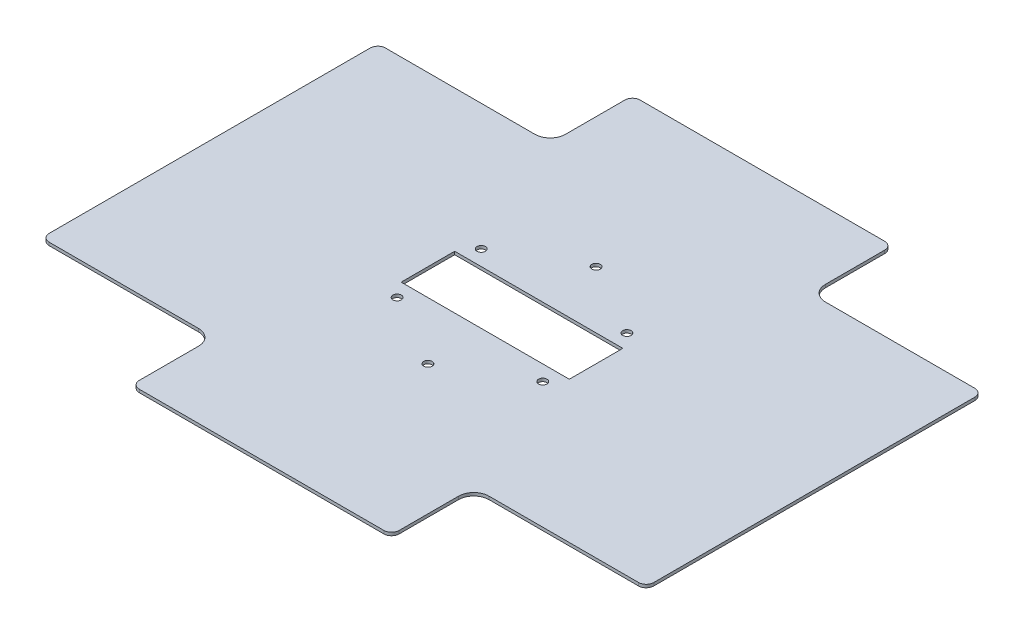
SolidWorks part; units mm, degrees
material "7075-T6, Пластина (SS)"
ref_plane "Спереди" through (0, 0, 0) normal (0, 0, 1) x (1, 0, 0)
ref_plane "Сверху" through (0, 0, 0) normal (0, 1, 0) x (1, 0, 0)
ref_plane "Справа" through (0, 0, 0) normal (1, 0, 0) x (0, 0, -1)
sketch "Эскиз1" plane through (0, 0, 0) normal (0, 1, 0) x (1, 0, 0)
  line L1 (-80, -163.8055) -> (80, -163.8055)
  line L2 (-197.7687, -105) -> (-197.7687, 105)
  line L3 (-80, 163.8055) -> (80, 163.8055)
  line L4 (197.7687, -105) -> (197.7687, 105)
  line L5 (-236.4266, 144.4996) -> (-147.9018, 144.4996) construction
  line L6 (-147.9018, 144.4996) -> (286.4952, 144.4996) construction
  line L18 (-284.5497, 0) -> (284.3305, 0) construction
  line L19 (-160.9018, 110) -> (-134.9018, 110)
  line L20 (-160.9018, 110) -> (-160.9018, 0)
  line L21 (-160.9018, 0) -> (-134.9018, 0)
  line L22 (-134.9018, 110) -> (-134.9018, 0)
  line L23 (-147.9018, -182.6295) -> (-147.9018, 219.9923) construction
  line L24 (-160.9018, 0) -> (-134.9018, 0)
  line L25 (-160.9018, 0) -> (-160.9018, -110)
  line L26 (-160.9018, -110) -> (-134.9018, -110)
  line L27 (-134.9018, 0) -> (-134.9018, -110)
  line L28 (-97.9018, -119.4996) -> (-197.9018, -119.4996)
  line L29 (-97.9018, 169.4996) -> (-197.9018, 169.4996)
  line L30 (-97.9018, 169.4996) -> (-97.9018, 119.4996)
  line L31 (-97.9018, 119.4996) -> (-197.9018, 119.4996)
  line L32 (-197.9018, 169.4996) -> (-197.9018, 119.4996)
  line L33 (-97.9018, 169.4996) -> (-197.9018, 119.4996) construction
  line L34 (-97.9018, 119.4996) -> (-197.9018, 169.4996) construction
  line L35 (-197.9018, -169.4996) -> (-197.9018, -119.4996)
  line L36 (-97.9018, -169.4996) -> (-197.9018, -169.4996)
  line L37 (-97.9018, -169.4996) -> (-97.9018, -119.4996)
  line L39 (-85, 120) -> (-85, 158.8055)
  line L40 (0, 262.7398) -> (0, -186.5795) construction
  line L41 (-192.7687, 110) -> (-95, 110)
  line L43 (-192.7687, -110) -> (-95, -110)
  line L44 (-85, -120) -> (-85, -158.8055)
  line L45 (85, 120) -> (85, 158.8055)
  line L46 (192.7687, 110) -> (95, 110)
  line L47 (192.7687, -110) -> (95, -110)
  line L48 (85, -120) -> (85, -158.8055)
  line L49 (97.9018, -169.4996) -> (97.9018, -119.4996)
  line L50 (97.9018, -169.4996) -> (197.9018, -169.4996)
  line L51 (197.9018, -169.4996) -> (197.9018, -119.4996)
  line L52 (97.9018, -119.4996) -> (197.9018, -119.4996)
  line L53 (160.9018, 0) -> (160.9018, -110)
  line L54 (160.9018, -110) -> (134.9018, -110)
  line L55 (134.9018, 0) -> (134.9018, -110)
  line L56 (160.9018, 0) -> (134.9018, 0)
  line L57 (160.9018, 110) -> (160.9018, 0)
  line L58 (160.9018, 0) -> (134.9018, 0)
  line L59 (134.9018, 110) -> (134.9018, 0)
  line L60 (160.9018, 110) -> (134.9018, 110)
  line L61 (97.9018, 119.4996) -> (197.9018, 119.4996)
  line L62 (197.9018, 169.4996) -> (197.9018, 119.4996)
  line L63 (97.9018, 169.4996) -> (197.9018, 169.4996)
  line L64 (97.9018, 169.4996) -> (97.9018, 119.4996)
  arc A0 (85, -120) -> (95, -110) centre (95, -120) cw
  arc A1 (85, 120) -> (95, 110) centre (95, 120) ccw
  arc A2 (-95, -110) -> (-85, -120) centre (-95, -120) cw
  arc A3 (-85, 120) -> (-95, 110) centre (-95, 120) cw
  arc A4 (192.7687, -110) -> (197.7687, -105) centre (192.7687, -105) ccw
  arc A5 (85, -158.8055) -> (80, -163.8055) centre (80, -158.8055) cw
  arc A6 (-85, -158.8055) -> (-80, -163.8055) centre (-80, -158.8055) ccw
  arc A7 (-192.7687, -110) -> (-197.7687, -105) centre (-192.7687, -105) cw
  arc A8 (-192.7687, 110) -> (-197.7687, 105) centre (-192.7687, 105) ccw
  arc A9 (197.7687, 105) -> (192.7687, 110) centre (192.7687, 105) ccw
  arc A10 (85, 158.8055) -> (80, 163.8055) centre (80, 158.8055) ccw
  arc A11 (-85, 158.8055) -> (-80, 163.8055) centre (-80, 158.8055) cw
  point P0 (0, 0)
  point P3 (85, -110)
  point P17 (-147.9018, 110)
  point P18 (-147.9018, 110)
  point P20 (-147.9018, 0)
  point P22 (-150, 134)
  point P37 (-147.9018, 144.4996)
  point P46 (85, 110)
  point P52 (-85, -110)
  point P55 (-85, 110)
  point P56 (-147.9018, 0)
  point P77 (197.7687, -110)
  point P80 (85, -163.8055)
  point P83 (-85, -163.8055)
  point P86 (-197.7687, -110)
  point P89 (-197.7687, 110)
  point P92 (197.7687, 110)
  point P95 (85, 163.8055)
  point P98 (-85, 163.8055)
  dimension "D2" = 50
  dimension "D6" = 10
  dimension "D4" = 5
  dimension "D3" = 26
  dimension "D5" = 338.9991
  dimension "D7" = 395.5373
  dimension "D8" = 110
  dimension "D9" = 170
  dimension "D10" = 100
  dimension "D13" = 9.4996
  dimension "D14" = 12.9018
sketch "Эскиз2" plane through (0, 0, 0) normal (0, 1, 0) x (1, 0, 0)
  line L0 (-162.9105, 114) -> (-136.9105, 114)
  line L1 (-162.9105, 114) -> (-162.9105, 0)
  line L2 (-162.9105, 0) -> (-136.9105, 0)
  line L3 (-136.9105, 114) -> (-136.9105, 0)
  line L4 (-149.9105, -192.6295) -> (-149.9105, 209.9923) construction
  line L5 (-162.9105, 0) -> (-136.9105, 0)
  line L6 (-162.9105, 0) -> (-162.9105, -114)
  line L7 (-162.9105, -114) -> (-136.9105, -114)
  line L8 (-136.9105, 0) -> (-136.9105, -114)
  line L9 (-99.9105, -123.5568) -> (-199.9105, -123.5568)
  line L10 (-99.9105, 163.4996) -> (-199.9105, 163.4996)
  line L11 (-99.9105, 163.4996) -> (-99.9105, 123.4996)
  line L12 (-99.9105, 123.4996) -> (-199.9105, 123.4996)
  line L13 (-199.9105, 163.4996) -> (-199.9105, 123.4996)
  line L14 (-199.9105, -163.5568) -> (-199.9105, -123.5568)
  line L15 (-99.9105, -163.5568) -> (-199.9105, -163.5568)
  line L16 (-99.9105, -163.5568) -> (-99.9105, -123.5568)
  line L17 (-284.5497, 0) -> (284.3305, 0) construction
  point P11 (-149.9105, 0)
  point P12 (-149.9105, 0)
sketch "Эскиз3" plane through (0, 0, 0) normal (0, 1, 0) x (1, 0, 0)
  line L0 (-89.8176, -177.9027) -> (70.2405, -177.9027)
  line L1 (-209.7886, -106.9112) -> (-209.7886, 106.8353)
  line L2 (-80.029, 172.0973) -> (50.2405, 172.0973)
  line L3 (170.2114, -106.9112) -> (170.2114, 103.9123)
  line L4 (-87.1938, 124.0033) -> (-87.1938, 164.9326)
  line L5 (-202.6239, 114) -> (-97.1971, 114)
  line L6 (-202.6239, -114.076) -> (-106.9857, -114.076)
  line L7 (-96.9823, -124.0793) -> (-96.9823, -170.738)
  line L8 (57.4052, 121.0803) -> (57.4052, 164.9326)
  line L9 (163.0467, 111.077) -> (67.4085, 111.077)
  line L10 (163.0467, -114.076) -> (87.4085, -114.076)
  line L11 (77.4052, -124.0793) -> (77.4052, -170.738)
  line L13 (-162.9105, 114) -> (-136.9105, 114) construction
  arc A0 (77.4052, -124.0793) -> (87.4085, -114.076) centre (87.4085, -124.0793) cw
  arc A1 (57.4052, 121.0803) -> (67.4085, 111.077) centre (67.4085, 121.0803) ccw
  arc A2 (-106.9857, -114.076) -> (-96.9823, -124.0793) centre (-106.9857, -124.0793) cw
  arc A3 (-87.1938, 124.0033) -> (-97.1971, 114) centre (-97.1971, 124.0033) cw
  arc A4 (-80.029, 172.0973) -> (-87.1938, 164.9326) centre (-80.029, 164.9326) ccw
  arc A5 (50.2405, 172.0973) -> (57.4052, 164.9326) centre (50.2405, 164.9326) cw
  arc A6 (170.2114, 103.9123) -> (163.0467, 111.077) centre (163.0467, 103.9123) ccw
  arc A7 (170.2114, -106.9112) -> (163.0467, -114.076) centre (163.0467, -106.9112) cw
  arc A8 (70.2405, -177.9027) -> (77.4052, -170.738) centre (70.2405, -170.738) ccw
  arc A9 (-89.8176, -177.9027) -> (-96.9823, -170.738) centre (-89.8176, -170.738) cw
  arc A10 (-209.7886, -106.9112) -> (-202.6239, -114.076) centre (-202.6239, -106.9112) ccw
  arc A11 (-209.7886, 106.8353) -> (-202.6239, 114) centre (-202.6239, 106.8353) cw
  point P36 (115.2276, 111.077)
  point P39 (-149.9105, 114)
  point P42 (-149.9105, 114)
  dimension "D3" = 10.0033
  dimension "D4" = 7.1647
  dimension "D1" = 380
  dimension "D2" = 350
  dimension "D5" = 112.8062
  dimension "D6" = 63.8267
  dimension "D7" = 61.0203
extrude "Бобышка-Вытянуть1" add sketch "Эскиз1" along normal blind 2 separate body contours A11 L39 A3 L41 L22 L27 L43 A2 L44 A6 L1 A5 L48 A0 L47 L55 L59 L46 A1 L45 A10 L3 | L4 A9 L46 L57 L53 L47 A4 | L46 L59 L56 L57 | L53 L56 L55 L47 | L27 L21 L25 L26 | L41 A8 L2 A7 L43 L25 L20 | L22 L19 L20 L21 region at (0, 0, 0) region at (-147.9018, 0, 55) region at (147.9018, 0, 55) region at (-179.3123, 0, 0) region at (-147.9018, 0, -55) region at (179.3123, 0, 0) region at (147.9018, 0, -55)
sketch "Эскиз4" plane through (0, 2, 0) normal (0, 1, 0) x (1, 0, 0)
  line L0 (197.7687, 0) -> (-197.7687, 0) construction
  line L1 (197.7687, -105) -> (197.7687, 105) construction
  line L2 (-197.7687, -105) -> (-197.7687, 105) construction
  line L3 (197.7687, 0) -> (10, 0) construction
  line L4 (-22, 0) -> (0, 0) construction
  line L5 (0, 0) -> (0, 55) construction
  circle A1 centre (0, 55) radius 2.75
  circle A2 centre (47.6314, 27.5) radius 2.75
  circle A3 centre (47.6314, -27.5) radius 2.75
  circle A4 centre (0, -55) radius 2.75
  circle A5 centre (-47.6314, -27.5) radius 2.75
  circle A6 centre (-47.6314, 27.5) radius 2.75
  circle A7 centre (0, 0) radius 55 construction
  point P14 (0, 0)
  point P29 (0, 0)
  dimension "D1" = 6
  dimension "D2" = 5.5
  dimension "D5" = 55
extrude "Вырез-Вытянуть1" cut sketch "Эскиз4" against normal through all
sketch "Эскиз5" plane through (0, 0, 0) normal (0, -1, 0) x (1, 0, 0)
  line L1 (-55, -17.5) -> (55, -17.5)
  line L2 (-55, -17.5) -> (-55, 17.5)
  line L3 (-55, 17.5) -> (55, 17.5)
  line L4 (55, -17.5) -> (55, 17.5)
  line L5 (-55, -17.5) -> (55, 17.5) construction
  line L6 (-55, 17.5) -> (55, -17.5) construction
  point P0 (0, 0)
  dimension "D1" = 110
  dimension "D2" = 35
extrude "Вырез-Вытянуть2" cut sketch "Эскиз5" against normal through all contours L3 L4 L1 L2
